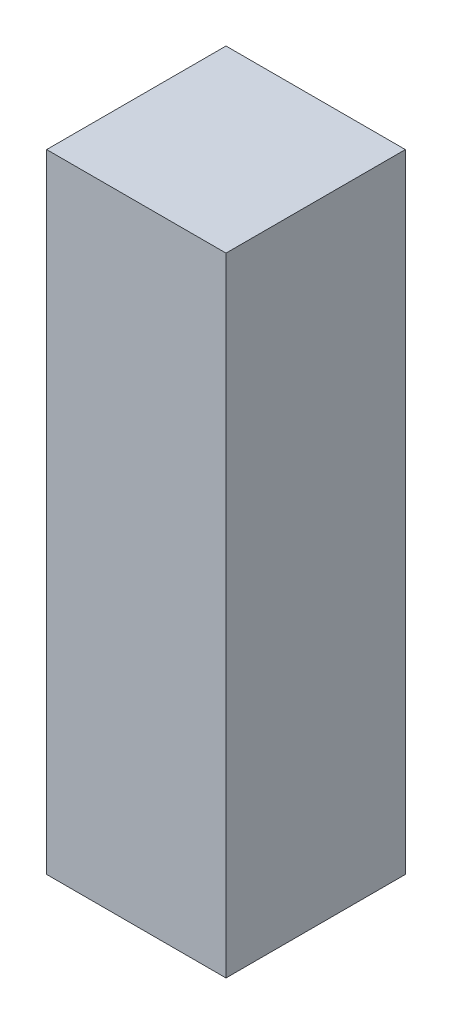
SolidWorks part; units mm, degrees
ref_plane "Front Plane" through (0, 0, 0) normal (0, 0, 1) x (1, 0, 0)
ref_plane "Top Plane" through (0, 0, 0) normal (0, 1, 0) x (1, 0, 0)
ref_plane "Right Plane" through (0, 0, 0) normal (1, 0, 0) x (0, 0, -1)
sketch "Sketch1" plane through (0, 0, 0) normal (0, 1, 0) x (1, 0, 0)
  line L1 (-10, 10) -> (10, 10)
  line L2 (-10, 10) -> (-10, -10)
  line L3 (-10, -10) -> (10, -10)
  line L4 (10, 10) -> (10, -10)
  line L5 (-10, 10) -> (10, -10) construction
  line L6 (-10, -10) -> (10, 10) construction
  point P0 (0, 0)
  dimension "D1" = 20
  dimension "D2" = 20
extrude "Boss-Extrude1" add sketch "Sketch1" along normal blind 70
